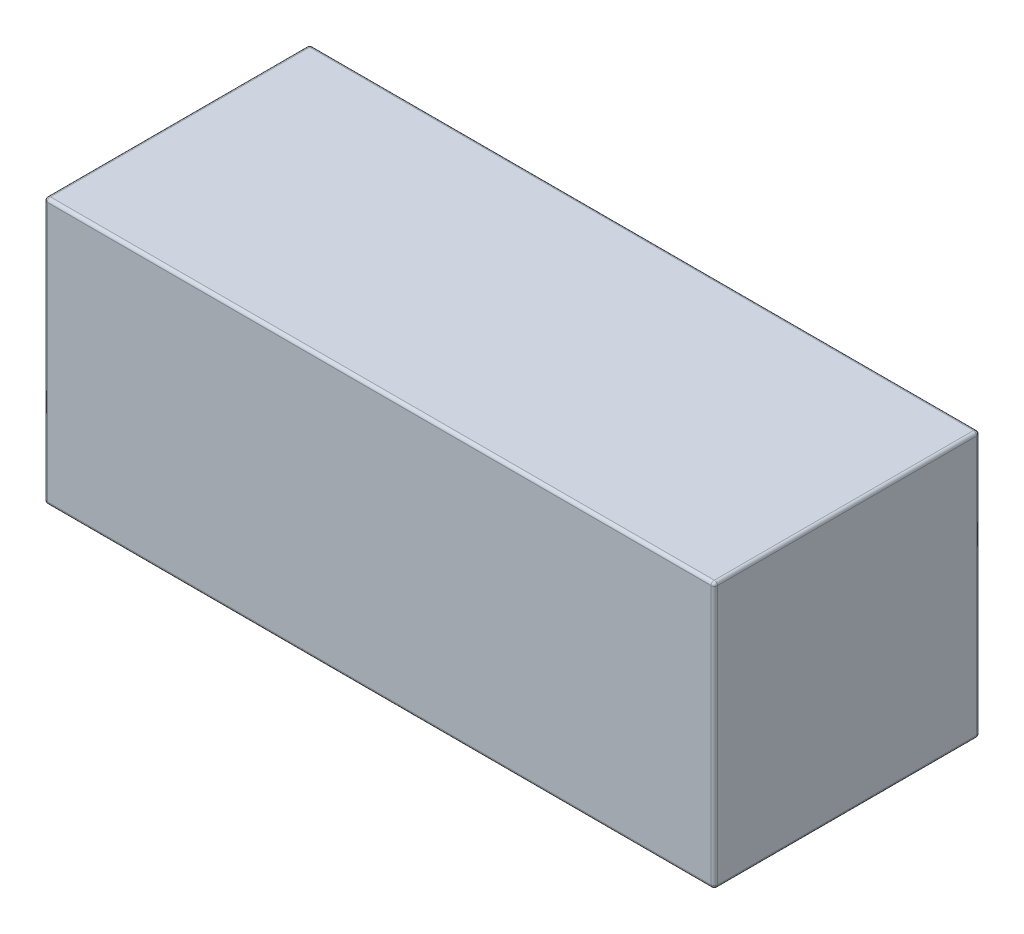
SolidWorks part; units mm, degrees
ref_plane "Plan de face" through (0, 0, 0) normal (0, 0, 1) x (1, 0, 0)
ref_plane "Plan de dessus" through (0, 0, 0) normal (0, 1, 0) x (1, 0, 0)
ref_plane "Plan de droite" through (0, 0, 0) normal (1, 0, 0) x (0, 0, -1)
sketch "Esquisse1" plane through (0, 0, 0) normal (0, 0, 1) x (1, 0, 0)
  line L1 (0, 0) -> (106, 0)
  line L2 (0, 0) -> (0, -42)
  line L3 (0, -42) -> (106, -42)
  line L4 (106, 0) -> (106, -42)
  dimension "D1" = 106
  dimension "D2" = 42
extrude "Boss.-Extru.1" add sketch "Esquisse1" along normal blind 42
sketch "Esquisse2" plane through (0, -42, 0) normal (0, -1, 0) x (1, 0, 0)
  line L1 (59.75, 38.25) -> (70.25, 38.25)
  line L2 (59.75, 38.25) -> (59.75, 27.75)
  line L3 (59.75, 27.75) -> (70.25, 27.75)
  line L4 (70.25, 38.25) -> (70.25, 27.75)
  line L5 (88.75, 3.75) -> (99.25, 3.75)
  line L6 (0, 0) -> (106, 0) construction
  line L7 (106, 42) -> (106, 0) construction
  line L8 (88.75, 3.75) -> (88.75, 14.25)
  line L9 (88.75, 14.25) -> (99.25, 14.25)
  line L10 (0, 42) -> (106, 42) construction
  line L11 (99.25, 3.75) -> (99.25, 14.25)
  line L12 (88.75, 27.75) -> (99.25, 27.75)
  line L13 (59.75, 14.25) -> (70.25, 14.25)
  line L14 (59.75, 14.25) -> (59.75, 3.75)
  line L15 (59.75, 3.75) -> (70.25, 3.75)
  line L16 (70.25, 14.25) -> (70.25, 3.75)
  line L17 (88.75, 27.75) -> (88.75, 38.25)
  line L18 (88.75, 38.25) -> (99.25, 38.25)
  line L19 (99.25, 27.75) -> (99.25, 38.25)
  point P4 (70.25, 9)
  point P7 (106, 21)
  point P10 (53, 42)
  point P11 (65, 38.25)
  point P16 (65, 3.75)
  point P20 (53, 0)
  point P21 (70.25, 33)
  point P29 (94, 27.75)
  point P30 (94, 14.25)
  point P31 (94, 38.25)
  dimension "D1" = 10.5
  dimension "D2" = 10.5
  dimension "D3" = 10.5
  dimension "D4" = 10.5
  dimension "D5" = 12
  dimension "D6" = 12
  dimension "D7" = 12
  dimension "D8" = 12
  dimension "D9" = 10.5
  dimension "D10" = 10.5
  dimension "D11" = 29
  dimension "D12" = 29
extrude "Enlèv. mat.-Extru.1" cut sketch "Esquisse2" against normal blind 4.5
ref_plane "Plan1" through (0, 0, 21) normal (0, 0, 1) x (1, 0, 0)
ref_plane "Plan2" through (53, 0, 0) normal (1, 0, 0) x (0, 0, -1)
ref_plane "Plan3" through (37, 0, 37) normal (0.7071, 0, 0.7071) x (0.7071, 0, -0.7071)
fillet "Congé1" radius 0.5 12 edges at (0, -42, 21) (53, -42, 42) (0, -21, 42) (106, -42, 21) (106, -21, 42) (53, -42, 0) (106, -21, 0) (0, -21, 0) (106, 0, 21) (53, 0, 42) (0, 0, 21) (53, 0, 0)
mirror "Symétrie1" about plane through (53, 0, 0) normal (1, 0, 0) of "Enlèv. mat.-Extru.1"
